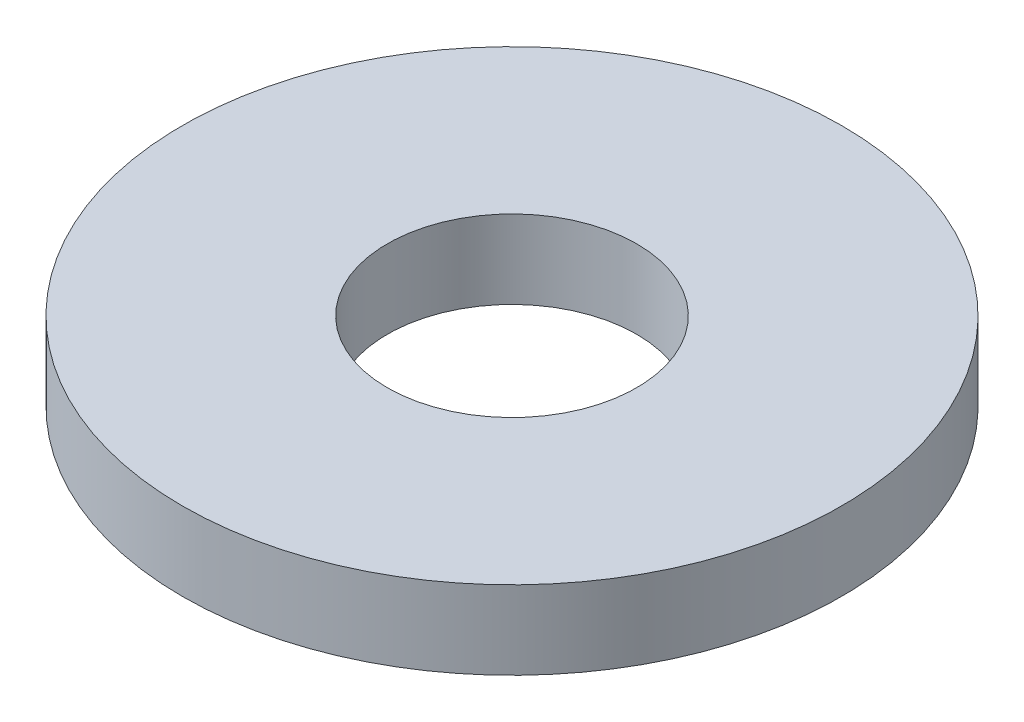
SolidWorks part; units mm, degrees
ref_plane "Front Plane" through (0, 0, 0) normal (0, 0, 1) x (1, 0, 0)
ref_plane "Top Plane" through (0, 0, 0) normal (0, 1, 0) x (1, 0, 0)
ref_plane "Right Plane" through (0, 0, 0) normal (1, 0, 0) x (0, 0, -1)
sketch "Sketch1" plane through (0, 0, 0) normal (0, 1, 0) x (1, 0, 0)
  circle A0 centre (0, 0) radius 92.5
  dimension "FLANGE_OD" = 185
extrude "Boss-Extrude1" add sketch "Sketch1" along normal blind 22
sketch "Sketch2" plane through (0, 0, 0) normal (0, 1, 0) x (1, 0, 0)
  circle A0 centre (0, 0) radius 35
  dimension "BORE_D" = 70
extrude "Cut-Extrude1" cut sketch "Sketch2" along normal through all
sketch "Sketch3" plane through (0, 22, 0) normal (0, 1, 0) x (1, 0, 0)
  circle A0 centre (0, 0) radius 19.8273 construction
  circle A1 centre (-19.8273, 0) radius 1.9669
  dimension "BOLT_D" = 3.9338
  dimension "BOLT_PCD" = 39.6546
extrude "Cut-Extrude2" cut sketch "Sketch3" against normal blind 20.8661 rebuild error yes
pattern_circular "CirPattern1" count 4 over 360 rebuild error yes
